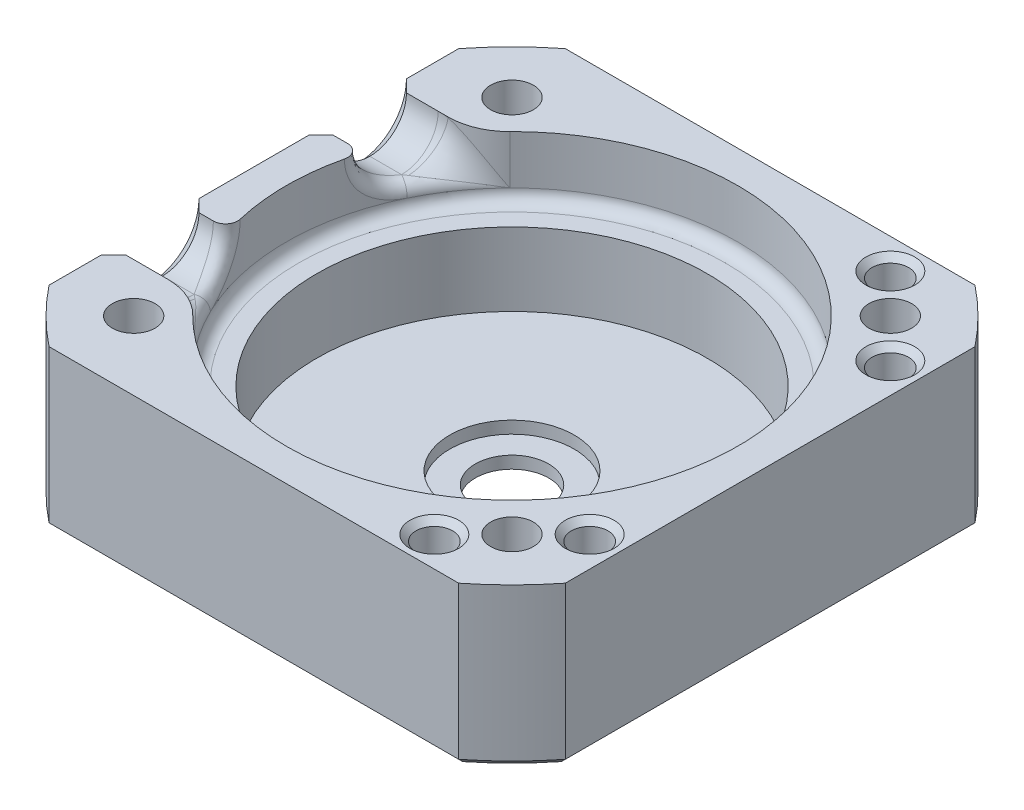
SolidWorks part; units mm, degrees
ref_plane "Front Plane" through (0, 0, 0) normal (0, 0, 1) x (1, 0, 0)
ref_plane "Top Plane" through (0, 0, 0) normal (0, 1, 0) x (1, 0, 0)
ref_plane "Right Plane" through (0, 0, 0) normal (1, 0, 0) x (0, 0, -1)
sketch "Sketch2" plane through (0, 0, 0) normal (0, 1, 0) x (1, 0, 0)
  line L1 (-21.15, 21.15) -> (21.15, 21.15)
  line L2 (-21.15, 21.15) -> (-21.15, -21.15)
  line L3 (-21.15, -21.15) -> (21.15, -21.15)
  line L4 (21.15, 21.15) -> (21.15, -21.15)
  line L5 (-21.15, 21.15) -> (21.15, -21.15) construction
  line L6 (-21.15, -21.15) -> (21.15, 21.15) construction
  point P0 (0, 0)
  dimension "D1" = 42.3
extrude "Boss-Extrude1" add sketch "Sketch2" along normal blind 13
sketch "Sketch3" plane through (0, 13, 0) normal (0, 1, 0) x (1, 0, 0)
  circle A0 centre (0, 0) radius 3
  dimension "D1" = 6
extrude "Cut-Extrude1" cut sketch "Sketch3" against normal through all
sketch "Sketch4" plane through (0, 13, 0) normal (0, 1, 0) x (1, 0, 0)
  line L1 (-15.5, 15.5) -> (15.5, 15.5) construction
  line L2 (-15.5, 15.5) -> (-15.5, -15.5) construction
  line L3 (-15.5, -15.5) -> (15.5, -15.5) construction
  line L4 (15.5, 15.5) -> (15.5, -15.5) construction
  line L5 (-15.5, 15.5) -> (15.5, -15.5) construction
  line L6 (-15.5, -15.5) -> (15.5, 15.5) construction
  circle A0 centre (-15.5, 15.5) radius 1.75
  circle A1 centre (15.5, 15.5) radius 1.75
  circle A2 centre (15.5, -15.5) radius 1.75
  circle A3 centre (-15.5, -15.5) radius 1.75
  point P0 (0, 0)
  point P16 (0, 0)
  dimension "D3" = 3.5
  dimension "D1" = 31
  dimension "D2" = 31
  dimension "D4" = 4
extrude "Cut-Extrude2" cut sketch "Sketch4" against normal through all
sketch "Sketch5" plane through (0, 13, 0) normal (0, 1, 0) x (1, 0, 0)
  circle A0 centre (0, 0) radius 27
  circle A1 centre (0, 0) radius 29.9106
  dimension "D1" = 54
extrude "Cut-Extrude4" cut sketch "Sketch5" against normal through all
sketch "Sketch6" plane through (0, 13, 0) normal (0, 1, 0) x (1, 0, 0)
  line L11 (-14.4914, 11.5) -> (-21.15, 11.5)
  line L12 (5.013, 21.15) -> (21.15, 5.013) construction
  line L13 (7.3751, 21.15) -> (21.15, 7.3751) construction
  line L14 (16.7833, 21.15) -> (-16.7833, 21.15) construction
  line L15 (21.15, -16.7833) -> (21.15, 16.7833) construction
  line L18 (-21.15, 16.7833) -> (-21.15, -16.7833) construction
  line L24 (-21.15, 11.5) -> (-21.15, 5.5)
  line L25 (-21.15, 5.5) -> (-17.6635, 5.5)
  line L26 (-17.6635, -5.5) -> (-21.15, -5.5)
  line L27 (-21.15, -5.5) -> (-21.15, -11.5)
  line L28 (-21.15, -11.5) -> (-14.4914, -11.5)
  line L29 (-21.15, 8.5) -> (-21.15, -8.5) construction
  arc A0 (-14.4914, 11.5) -> (-14.4914, -11.5) centre (0, 0) cw
  arc A2 (-17.6635, 5.5) -> (-17.6635, -5.5) centre (0, 0) ccw
  circle A3 centre (0, 0) radius 11 construction
  circle A5 centre (15.5, 15.5) radius 1.75 construction
  arc A6 (-14.4914, -11.5) -> (-14.4914, 11.5) centre (0, 0) ccw
  circle M13 centre (0, 0) radius 3
  line M14 (-16.7833, -21.15) -> (16.7833, -21.15)
  line M20 (-21.15, 16.7833) -> (-21.15, -16.7833)
  dimension "D1" = 6
  dimension "D3" = 18.5
  dimension "D5" = 22
  dimension "D2" = 17
  dimension "D4" = 45
extrude "Cut-Extrude5" cut sketch "Sketch6" against normal offset from surface (11 mm away) 2 contours A2 A0 M14 M20 M13 region at (17.9577, 13, 0) up to face at (-15.5, 0, 17.25)
sketch "Sketch7" plane through (0, 2, 0) normal (0, 1, 0) x (1, 0, 0)
  circle A0 centre (0, 0) radius 5.1
  dimension "D1" = 10.2
extrude "Cut-Extrude6" cut sketch "Sketch7" against normal blind 1
sketch "Sketch8" plane through (0, 2, 0) normal (0, 1, 0) x (1, 0, 0)
  line L6 (-21.15, 5.5) -> (-17.6635, 5.5)
  line L7 (-21.15, 5.5) -> (-17.6635, 5.5)
  line L8 (-17.6635, -5.5) -> (-21.15, -5.5)
  line L9 (-17.6635, -5.5) -> (-21.15, -5.5)
  line L10 (-21.15, -5.5) -> (-21.15, -11.5)
  line L11 (-21.15, -5.5) -> (-21.15, -11.5)
  line L18 (-21.15, -11.5) -> (-14.4914, -11.5)
  line L19 (-21.15, -11.5) -> (-14.4914, -11.5)
  line L20 (-14.4914, 11.5) -> (-21.15, 11.5)
  line L21 (-14.4914, 11.5) -> (-21.15, 11.5)
  line L22 (-21.15, 11.5) -> (-21.15, 5.5)
  line L23 (-21.15, 11.5) -> (-21.15, 5.5)
  circle A0 centre (0, 0) radius 16
  arc A3 (-17.6635, 5.5) -> (-17.6635, -5.5) centre (0, 0) ccw
  arc A4 (-14.4914, -11.5) -> (-14.4914, 11.5) centre (0, 0) ccw
  arc A5 (-17.6635, 5.5) -> (-17.6635, -5.5) centre (0, 0) ccw
  arc A6 (-14.4914, -11.5) -> (-14.4914, 11.5) centre (0, 0) ccw
  dimension "D1" = 32
  dimension "D2" = 0
extrude "Boss-Extrude2" add sketch "Sketch8" along normal offset from surface (6 mm away) 5 up to face at (-3.1909, 13, 0)
sketch "Sketch9" plane through (0, 13, 0) normal (0, 1, 0) x (1, 0, 0)
  line L0 (12.318, 18.682) -> (18.682, 12.318) construction
  line L1 (-16.7833, -21.15) -> (16.7833, -21.15) construction
  line L2 (-21.15, 0) -> (21.15, 0) construction
  line L3 (-21.15, 5.5) -> (-21.15, -5.5) construction
  line L4 (21.15, -16.7833) -> (21.15, 16.7833) construction
  line L5 (12.318, -18.682) -> (18.682, -12.318) construction
  circle A0 centre (15.5, 15.5) radius 1.75 construction
  circle A1 centre (12.318, 18.682) radius 1.5
  circle A2 centre (18.682, 12.318) radius 1.5
  circle A7 centre (18.682, -12.318) radius 1.5
  circle A8 centre (12.318, -18.682) radius 1.5
  point P2 (15.5, 15.5)
  dimension "D2" = 3
  dimension "D3" = 3
  dimension "D1" = 4.5
  dimension "D4" = 45
extrude "Cut-Extrude7" cut sketch "Sketch9" against normal blind 3
sketch "Sketch10" plane through (0, 8, 0) normal (0, 1, 0) x (1, 0, 0)
  line L0 (-21.15, 5.5) -> (-17.6635, 5.5) construction
  line L2 (-17.6635, -5.5) -> (-21.15, -5.5) construction
  line L3 (-14.4914, 11.5) -> (-21.15, 11.5)
  line L4 (-21.15, 11.5) -> (-21.15, 5.5)
  line L5 (-21.15, 5.5) -> (-17.6635, 5.5)
  line L6 (-17.6635, -5.5) -> (-21.15, -5.5)
  line L7 (-21.15, -5.5) -> (-21.15, -11.5)
  line L8 (-21.15, -11.5) -> (-14.4914, -11.5)
  arc A0 (-14.4914, 11.5) -> (-17.6635, 5.5) centre (0, 0) ccw
  arc A1 (-14.4914, -11.5) -> (-17.6635, -5.5) centre (0, 0) cw
extrude "Boss-Extrude3" add sketch "Sketch10" along normal blind 2
chamfer "Chamfer1" distance 2 angle 45 4 edges at (15.5, 0, -13.75) (-15.5, 0, -13.75) (-15.5, 0, 17.25) (15.5, 0, 17.25)
chamfer "Chamfer3" distance 0.5 angle 45 4 edges at (12.318, 13, -17.182) (18.682, 13, -10.818) (18.682, 13, 10.818) (12.318, 13, 17.182)
chamfer "Chamfer4" distance 0.5 angle 45 8 edges at (19.0919, 0, 19.0919) (0, 0, 21.15) (-19.0919, 0, 19.0919) (-21.15, 0, 0) (-19.0919, 0, -19.0919) (0, 0, -21.15) (19.0919, 0, -19.0919) (21.15, 0, 0)
fillet "Fillet10" radius 5 2 edges at (-14.4914, 11.5, -11.5) (-14.4914, 11.5, 11.5)
fillet "Fillet11" radius 3 2 edges at (-19.4068, 10, 5.5) (-19.4068, 10, -5.5)
fillet "Fillet6" radius 1 1 edges at (0, 8, 18.5)
fillet "Fillet9" radius 1 4 edges at (-14.9715, 10, -10.8675) (-14.9715, 10, 10.8675) (-17.4652, 11.1992, 6.1006) (-17.3158, 10.7529, -6.5124)
fillet "Fillet8" radius 3 6 edges at (-18.9416, 10, -11.5) (-18.9416, 10, 11.5) (-14.8803, 9.8805, -11.856) (-16.1948, 10, -11.5291) (-14.8803, 9.8805, 11.856) (-16.1948, 10, 11.5291)
chamfer "Chamfer5" distance 1 angle 45 4 edges at (-21.15, 10.8787, 10.6213) (-21.15, 10.8787, 6.3787) (-21.15, 10.8787, -6.3787) (-21.15, 10.8787, -10.6213)
